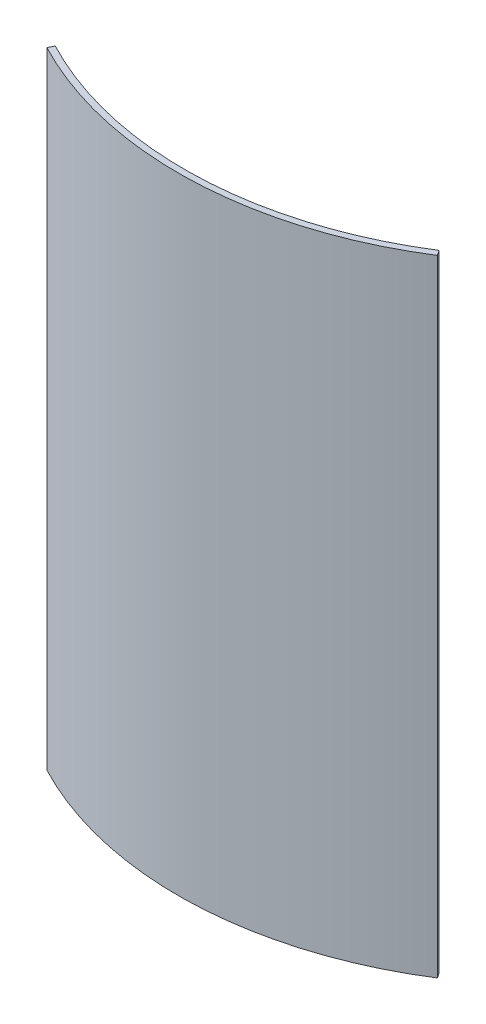
SolidWorks part; units mm, degrees
ref_plane "Front Plane" through (0, 0, 0) normal (0, 0, 1) x (1, 0, 0)
ref_plane "Top Plane" through (0, 0, 0) normal (0, 1, 0) x (1, 0, 0)
ref_plane "Right Plane" through (0, 0, 0) normal (1, 0, 0) x (0, 0, -1)
sketch "Sketch1" plane through (0, 0, 0) normal (0, 1, 0) x (1, 0, 0)
  line L0 (-34.8119, -66.3524) -> (-35.3862, -67.4852)
  line L2 (40.7508, -64.388) -> (40.0569, -63.3242)
  circle A0 centre (0, 0) radius 76.2 construction
  arc A1 (-35.3862, -67.4852) -> (40.7508, -64.388) centre (0, 0) ccw
  circle A2 centre (0, 0) radius 74.93 construction
  arc A3 (40.0569, -63.3242) -> (-34.8119, -66.3524) centre (0, 0) cw
extrude "Boss-Extrude1" add sketch "Sketch1" along normal blind 127
